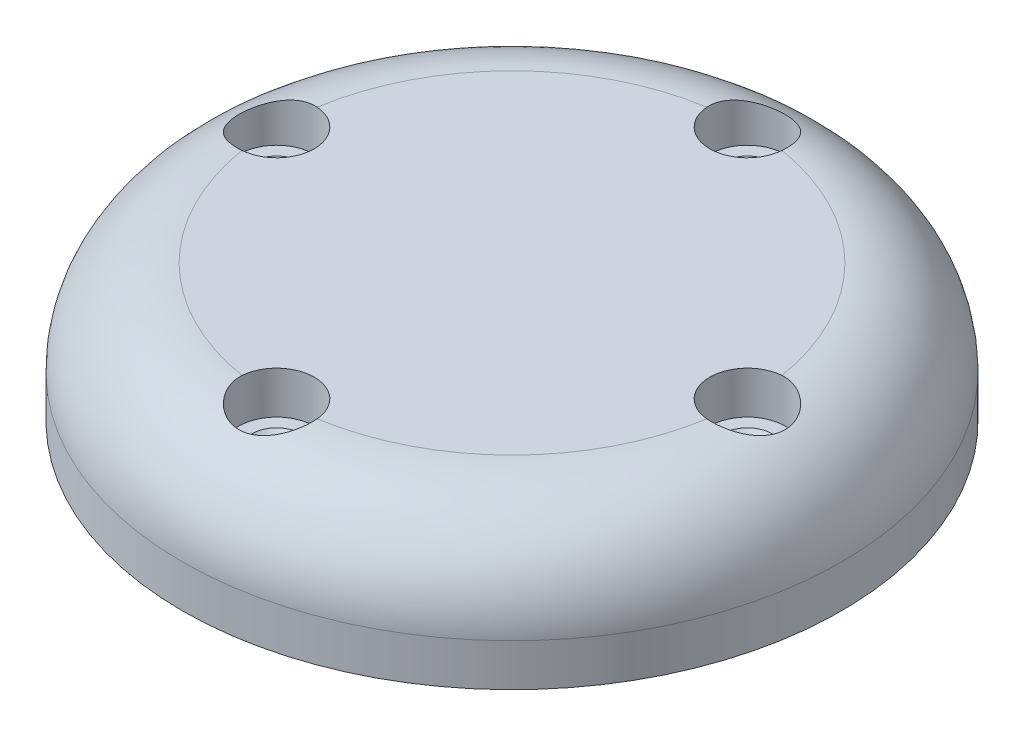
SolidWorks part; units mm, degrees
material "ABS"
ref_plane "Front Plane" through (0, 0, 0) normal (0, 0, 1) x (1, 0, 0)
ref_plane "Top Plane" through (0, 0, 0) normal (0, 1, 0) x (1, 0, 0)
ref_plane "Right Plane" through (0, 0, 0) normal (1, 0, 0) x (0, 0, -1)
sketch "Sketch1" plane through (0, 0, 0) normal (0, 1, 0) x (1, 0, 0)
  circle A0 centre (0, 0) radius 35
  circle A2 centre (0, 0) radius 13
  circle A3 centre (0, 0) radius 14
  dimension "D1" = 70
  dimension "D3" = 26
  dimension "D4" = 28
extrude "Boss-Extrude1" add sketch "Sketch1" along normal blind 18 from offset 3 contours A0 region at (-34.0101, 0, 0)
extrude "Boss-Extrude2" add sketch "Sketch1<3>" against normal blind 3 from surface contours A3 starting at face at (0, 21, 14)
sketch "Sketch1<3>" plane through (0, 0, 0) normal (0, 1, 0) x (1, 0, 0) same geometry as "Sketch1"
extrude "Boss-Extrude3" add sketch "Sketch1<4>" along normal up to surface (18 mm away) from offset 9 contours A3 region at (-13.604, 0, 0) up to face at (0, 18, 14)
sketch "Sketch1<4>" plane through (0, 0, 0) normal (0, 1, 0) x (1, 0, 0) same geometry as "Sketch1"
sketch "Sketch2" plane through (0, 21, 0) normal (0, 1, 0) x (1, 0, 0)
  circle A0 centre (0, 0) radius 25 construction
  circle A1 centre (0, -25) radius 4
  circle A2 centre (-25, 0) radius 4
  circle A3 centre (0, 25) radius 4
  circle A4 centre (25, 0) radius 4
  circle A5 centre (0, -25) radius 2.1
  circle A6 centre (-25, 0) radius 2.1
  circle A7 centre (0, 25) radius 2.1
  circle A8 centre (25, 0) radius 2.1
  point P13 (0, 0)
  point P21 (0, 0)
  dimension "D1" = 8
  dimension "D3" = 50
  dimension "D4" = 4.2
  dimension "D2" = 4
  dimension "D5" = 4
extrude "Cut-Extrude1" cut sketch "Sketch2" against normal up to next contours A5 | A6 | A8 | A7 region at (0, 21, 25)
extrude "Cut-Extrude2" cut sketch "Sketch2<3>" against normal blind 4.5
sketch "Sketch2<3>" plane through (0, 21, 0) normal (0, 1, 0) x (1, 0, 0) same geometry as "Sketch2"
chamfer "Chamfer1" distance 0.5 angle 45 4 edges at (25, 16.5, 2.1) (0, 16.5, 27.1) (-25, 16.5, 2.1) (0, 16.5, -22.9)
extrude "Boss-Extrude4" add sketch "Sketch1<6>" along normal blind 4.84 from offset 3 contours A3 | A2
sketch "Sketch1<6>" plane through (0, 0, 0) normal (0, 1, 0) x (1, 0, 0) same geometry as "Sketch1"
sketch "Sketch3" plane through (0, 18, 0) normal (0, -1, 0) x (1, 0, 0)
  circle A0 centre (0, 0) radius 13
extrude "Boss-Extrude5" add sketch "Sketch3" along normal blind 1
sketch "Sketch4" plane through (0, 3, 0) normal (0, -1, 0) x (1, 0, 0)
  circle A0 centre (0, 0) radius 35
  dimension "D1" = 70
extrude "Cut-Extrude3" cut sketch "Sketch4" against normal blind 3.5
fillet "Fillet1" radius 10 1 edges at (0, 21, 35)
